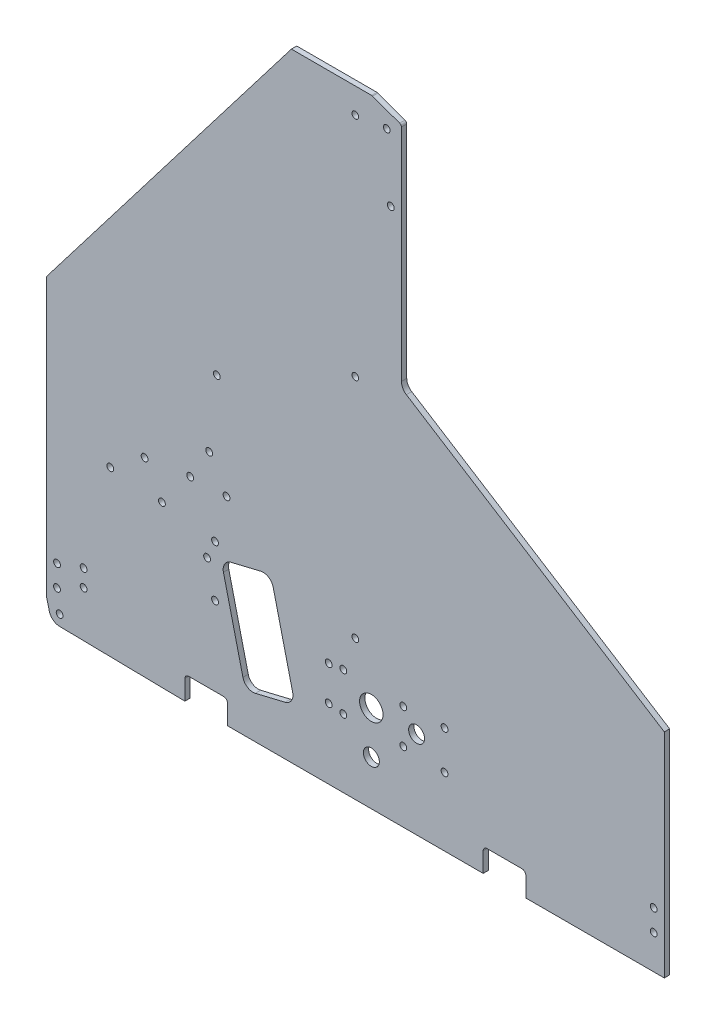
SolidWorks part; units mm, degrees
ref_plane "Front Plane" through (0, 0, 0) normal (0, 0, 1) x (1, 0, 0)
ref_plane "Top Plane" through (0, 0, 0) normal (0, 1, 0) x (1, 0, 0)
ref_plane "Right Plane" through (0, 0, 0) normal (1, 0, 0) x (0, 0, -1)
sketch "Sketch1" plane through (0, 0, 0) normal (0, 0, 1) x (1, 0, 0)
  line L0 (82.55, -20.32) -> (82.55, -6.35)
  line L2 (0, 0) -> (0, 157.48)
  line L4 (368.3, -20.32) -> (368.3, 106.68)
  line L5 (82.55, -6.35) -> (107.95, -6.35)
  line L6 (107.95, -6.35) -> (107.95, -20.32)
  line L7 (107.95, -20.32) -> (260.35, -20.32)
  line L8 (260.35, -20.32) -> (260.35, -6.35)
  line L9 (260.35, -6.35) -> (285.75, -6.35)
  line L10 (285.75, -6.35) -> (285.75, -20.32)
  line L11 (285.75, -20.32) -> (368.3, -20.32)
  line L12 (361.95, 12.7) -> (368.3, 12.7) construction
  line L13 (0, 0) -> (6.35, 0) construction
  line L14 (0.1896, -7.8901) -> (1.7771, -14.2401)
  line L15 (7.8295, -19.0491) -> (82.55, -20.32)
  line L16 (0, 0) -> (0, -6.35)
  line L17 (85.725, 97.155) -> (82.9754, 95.5675) construction
  line L18 (97.0634, 115.6163) -> (58.5686, 93.3913) construction
  line L19 (97.0634, 115.6163) -> (107.3822, 97.7437) construction
  line L20 (58.5686, 93.3913) -> (68.8873, 75.5187) construction
  line L21 (107.3822, 97.7437) -> (68.8873, 75.5187) construction
  line L22 (97.0634, 115.6163) -> (68.8873, 75.5187) construction
  line L23 (58.5686, 93.3913) -> (107.3822, 97.7437) construction
  line L24 (7.9375, -12.7) -> (95.7973, 60.4105) construction
  line L25 (184.15, 62.98) -> (184.15, 197.98) construction
  line L26 (184.15, 197.98) -> (184.15, 332.98) construction
  line L27 (355.6, 335.28) -> (330.2, 335.28) construction
  line L28 (330.2, 335.28) -> (330.2, 220.98) construction
  line L29 (330.2, 220.98) -> (355.6, 220.98) construction
  line L30 (355.6, 220.98) -> (355.6, 335.28) construction
  line L31 (184.15, 347.98) -> (184.15, 269.4703) construction
  line L32 (12.7, 335.28) -> (38.1, 335.28) construction
  line L33 (38.1, 335.28) -> (38.1, 220.98) construction
  line L34 (12.7, 220.98) -> (12.7, 335.28) construction
  line L35 (38.1, 220.98) -> (12.7, 220.98) construction
  line L36 (194.15, 347.98) -> (211.6138, 341.63)
  line L37 (184.15, 347.98) -> (146.05, 347.98)
  line L38 (184.15, 347.98) -> (194.15, 347.98)
  line L39 (348.5362, 347.98) -> (413.4623, 347.98)
  line L40 (348.5362, 347.98) -> (211.6138, 347.98) construction
  line L42 (146.05, 347.98) -> (0, 157.48)
  line L44 (211.6138, 341.63) -> (211.6138, 205.74)
  line L45 (211.6138, 205.74) -> (368.3, 106.68)
  line L46 (194.15, 347.98) -> (-141.0713, 347.98) construction
  circle A0 centre (6.35, 0) radius 2.032
  circle A1 centre (6.35, 12.7) radius 2.032
  circle A2 centre (361.95, 0) radius 2.032
  circle A3 centre (361.95, 12.7) radius 2.032
  arc A5 (1.7771, -14.2401) -> (7.8295, -19.0491) centre (7.9375, -12.7) ccw
  circle A6 centre (7.9375, -12.7) radius 2.032
  arc A7 (0, -6.35) -> (0.1896, -7.8901) centre (6.35, -6.35) ccw
  circle A8 centre (38.1, 78.105) radius 2.032
  circle A9 centre (85.725, 97.155) radius 2.032
  circle A10 centre (58.5686, 93.3913) radius 2.032
  circle A11 centre (68.8873, 75.5187) radius 2.032
  circle A12 centre (107.3822, 97.7437) radius 2.032
  circle A13 centre (97.0634, 115.6163) radius 2.032
  circle A14 centre (95.7973, 60.4105) radius 2.032
  circle A15 centre (184.15, 62.98) radius 2
  circle A16 centre (184.15, 197.98) radius 2
  circle A17 centre (184.15, 332.98) radius 2
  circle A18 centre (63.5, 316.23) radius 2.032
  circle A19 centre (101.6, 157.48) radius 2.032
  circle A20 centre (355.6, 335.28) radius 2.032
  circle A21 centre (330.2, 335.28) radius 2.032
  circle A22 centre (355.6, 220.98) radius 2.032
  circle A23 centre (330.2, 220.98) radius 2.032
  circle A24 centre (12.7, 335.28) radius 2.032
  circle A25 centre (38.1, 335.28) radius 2.032
  circle A26 centre (12.7, 220.98) radius 2.032
  circle A27 centre (38.1, 220.98) radius 2.032
  circle A28 centre (202.8819, 335.28) radius 2
  circle A29 centre (205.2638, 296.418) radius 2.032
  point P82 (184.15, 347.98)
  point P83 (202.8819, 344.805)
  dimension "D6" = 4.064
  dimension "D10" = 6.35
  dimension "D11" = 4.064
  dimension "D17" = 38.1
  dimension "D27" = 4
  dimension "D31" = 4.064
  dimension "D32" = 38.1
  dimension "D36" = 4.064
  dimension "D47" = 45.212
  dimension "D48" = 4.064
  dimension "D2" = 127
  dimension "D3" = 13.97
  dimension "D4" = 25.4
  dimension "D5" = 152.4
  dimension "D7" = 12.7
  dimension "D8" = 6.35
  dimension "D9" = 20.32
  dimension "D12" = 12.7
  dimension "D13" = 1.5875
  dimension "D14" = 82.55
  dimension "D15" = 368.3
  dimension "D16" = 6.35
  dimension "D18" = 98.425
  dimension "D19" = 47.625
  dimension "D20" = 19.05
  dimension "D21" = 3.175
  dimension "D22" = 60
  dimension "D23" = 20.6375
  dimension "D24" = 44.45
  dimension "D25" = 38.1
  dimension "D26" = 114.3
  dimension "D28" = 135
  dimension "D29" = 12.7
  dimension "D30" = 15
  dimension "D33" = 63.5
  dimension "D34" = 27.4638
  dimension "D35" = 101.6
  dimension "D37" = 114.3
  dimension "D38" = 25.4
  dimension "D39" = 12.7
  dimension "D40" = 157.48
  dimension "D41" = 142.24
  dimension "D42" = 368.3
  dimension "D43" = 10
  dimension "D44" = 6.35
  dimension "D45" = 31.75
  dimension "D46" = 6.35
  dimension "D49" = 6.35
extrude "Boss-Extrude1" add sketch "Sketch1" along normal blind 3.175 contours L16 A7 L14 A5 L15 L2 A0 A1 A6 region at (167.8922, 118.3155, 0)
fillet "Fillet1" radius 2.286 4 edges at (285.75, -6.35, 1.5875) (107.95, -6.35, 1.5875) (260.35, -6.35, 1.5875) (82.55, -6.35, 1.5875)
fillet "Fillet2" radius 6.35 1 edges at (211.6138, 205.74, 1.5875)
sketch "Sketch2" plane through (0, 0, 0) normal (0, 0, -1) x (-1, 0, 0)
  circle A0 centre (-100.5528, 71.086) radius 2.032 construction
  circle A1 centre (-100.5528, 40.606) radius 2.032 construction
  circle A2 centre (-22.225, 18.2025) radius 2.032 construction
  circle A3 centre (-22.225, 8.0425) radius 2.032 construction
  circle A4 centre (-100.5528, 71.086) radius 2.032
  circle A5 centre (-100.5528, 40.606) radius 2.032
  circle A6 centre (-22.225, 18.2025) radius 2.032
  circle A7 centre (-22.225, 8.0425) radius 2.032
extrude "Cut-Extrude1" cut sketch "Sketch2" against normal through all
fillet "Fillet3" radius 1.5875 2 edges at (211.6138, 341.63, 1.5875) (194.15, 347.98, 1.5875)
sketch "Sketch3" plane through (0, 0, 3.175) normal (0, 0, 1) x (1, 0, 0)
  line L0 (132.9524, 63.2646) -> (132.7215, 64.2281) construction
  line L1 (128.3814, 66.8897) -> (110.6828, 62.6472) construction
  line L2 (114.5132, 58.4237) -> (126.8822, 61.3887) construction
  line L3 (108.0212, 58.3071) -> (108.2522, 57.3436) construction
  line L4 (131.2006, 57.703) -> (140.0164, 20.9265) construction
  line L5 (144.0993, 16.7636) -> (132.9524, 63.2646) construction
  line L6 (108.2522, 57.3436) -> (119.3991, 10.8426) construction
  line L7 (121.1509, 16.4042) -> (112.3351, 53.1807) construction
  line L8 (119.3991, 10.8426) -> (119.6301, 9.8791) construction
  line L9 (144.3303, 15.8001) -> (144.0993, 16.7636) construction
  line L10 (137.8383, 15.6835) -> (125.4694, 12.7185) construction
  line L11 (123.9701, 7.2175) -> (141.6687, 11.4601) construction
  line L12 (132.9524, 63.2646) -> (132.7215, 64.2281)
  line L13 (128.3814, 66.8897) -> (110.6828, 62.6472)
  line L14 (114.5132, 58.4237) -> (126.8822, 61.3887)
  line L15 (108.0212, 58.3071) -> (108.2522, 57.3436)
  line L16 (131.2006, 57.703) -> (140.0164, 20.9265)
  line L17 (144.0993, 16.7636) -> (132.9524, 63.2646)
  line L18 (108.2522, 57.3436) -> (119.3991, 10.8426)
  line L19 (121.1509, 16.4042) -> (112.3351, 53.1807)
  line L20 (119.3991, 10.8426) -> (119.6301, 9.8791)
  line L21 (144.3303, 15.8001) -> (144.0993, 16.7636)
  line L22 (137.8383, 15.6835) -> (125.4694, 12.7185)
  line L23 (123.9701, 7.2175) -> (141.6687, 11.4601)
  line L24 (127.7894, 69.3598) -> (110.0908, 65.1172)
  line L25 (105.5512, 57.715) -> (105.7822, 56.7515)
  line L26 (105.7822, 56.7515) -> (116.9291, 10.2505)
  line L27 (116.9291, 10.2505) -> (117.16, 9.287)
  line L28 (124.5622, 4.7475) -> (142.2608, 8.99)
  line L29 (146.8003, 16.3922) -> (146.5694, 17.3557)
  line L30 (146.5694, 17.3557) -> (135.4225, 63.8567)
  line L31 (135.4225, 63.8567) -> (135.1915, 64.8202)
  arc A0 (132.7215, 64.2281) -> (128.6308, 66.9403) centre (129.2206, 63.3889) ccw construction
  arc A1 (110.6828, 62.6472) -> (110.4377, 62.5791) centre (111.522, 59.1463) ccw construction
  arc A2 (128.6308, 66.9403) -> (128.3814, 66.8897) centre (129.2206, 63.3889) ccw construction
  arc A3 (110.4377, 62.5791) -> (108.0212, 58.3071) centre (111.522, 59.1463) ccw construction
  arc A4 (119.6301, 9.8791) -> (123.7207, 7.1669) centre (123.1309, 10.7183) ccw construction
  arc A5 (141.9139, 11.5281) -> (144.3303, 15.8001) centre (140.8295, 14.9609) ccw construction
  arc A6 (141.6687, 11.4601) -> (141.9139, 11.5281) centre (140.8295, 14.9609) ccw construction
  arc A7 (123.7207, 7.1669) -> (123.9701, 7.2175) centre (123.1309, 10.7183) ccw construction
  arc A8 (132.7215, 64.2281) -> (128.6308, 66.9403) centre (129.2206, 63.3889) ccw
  arc A9 (110.6828, 62.6472) -> (110.4377, 62.5791) centre (111.522, 59.1463) ccw
  arc A10 (128.6308, 66.9403) -> (128.3814, 66.8897) centre (129.2206, 63.3889) ccw
  arc A11 (110.4377, 62.5791) -> (108.0212, 58.3071) centre (111.522, 59.1463) ccw
  arc A12 (119.6301, 9.8791) -> (123.7207, 7.1669) centre (123.1309, 10.7183) ccw
  arc A13 (141.9139, 11.5281) -> (144.3303, 15.8001) centre (140.8295, 14.9609) ccw
  arc A14 (141.6687, 11.4601) -> (141.9139, 11.5281) centre (140.8295, 14.9609) ccw
  arc A15 (123.7207, 7.1669) -> (123.9701, 7.2175) centre (123.1309, 10.7183) ccw
  arc A16 (110.0908, 65.1172) -> (109.6726, 65.0012) centre (111.522, 59.1463) ccw
  arc A17 (109.6726, 65.0012) -> (105.5512, 57.715) centre (111.522, 59.1463) ccw
  arc A18 (117.16, 9.287) -> (124.1369, 4.6613) centre (123.1309, 10.7183) ccw
  arc A19 (124.1369, 4.6613) -> (124.5622, 4.7475) centre (123.1309, 10.7183) ccw
  arc A20 (142.2608, 8.99) -> (142.6789, 9.1061) centre (140.8295, 14.9609) ccw
  arc A21 (142.6789, 9.1061) -> (146.8003, 16.3922) centre (140.8295, 14.9609) ccw
  arc A22 (135.1915, 64.8202) -> (128.2147, 69.446) centre (129.2206, 63.3889) ccw
  arc A23 (128.2147, 69.446) -> (127.7894, 69.3598) centre (129.2206, 63.3889) ccw
  ellipse E0 centre (124.5974, 48.8487) end of major axis (128.5376, 61.3578) minor radius 6 (131.2006, 57.703) -> (126.8822, 61.3887) ccw construction
  ellipse E1 centre (122.2349, 48.2824) end of major axis (113.0518, 57.6456) minor radius 6 (114.5132, 58.4237) -> (112.3351, 53.1807) ccw construction
  ellipse E2 centre (127.7541, 25.2585) end of major axis (131.6942, 37.7675) minor radius 6 (121.1509, 16.4042) -> (125.4694, 12.7185) ccw construction
  ellipse E3 centre (130.1166, 25.8248) end of major axis (139.2998, 16.4616) minor radius 6 (137.8383, 15.6835) -> (140.0164, 20.9265) ccw construction
  ellipse E4 centre (124.5974, 48.8487) end of major axis (128.5376, 61.3578) minor radius 6 (131.2006, 57.703) -> (126.8822, 61.3887) ccw
  ellipse E5 centre (122.2349, 48.2824) end of major axis (131.4181, 38.9192) minor radius 6 (114.5132, 58.4237) -> (112.3351, 53.1807) ccw
  ellipse E6 centre (127.7541, 25.2585) end of major axis (123.8139, 12.7495) minor radius 6 (121.1509, 16.4042) -> (125.4694, 12.7185) ccw
  ellipse E7 centre (130.1166, 25.8248) end of major axis (139.2998, 16.4616) minor radius 6 (137.8383, 15.6835) -> (140.0164, 20.9265) ccw
  dimension "D1" = 2.54
extrude "Cut-Extrude2" cut sketch "Sketch3" against normal through all contours A22 A23 L24 A16 A17 L25 L26 L27 A18 A19 L28 A20 A21 L29 L30 L31 A15 A12 L20 L18 L15 A11 A9 L13 A10 A8 L12 L17 L21 A13 A14 L23 | A12 A15 L23 A14 A13 L21 L17 L12 A8 A10 L13 A9 A11 L15 L18 L20 E7 L22 E6 L19 E5 L14 E4 L16 | L22 E7 L16 E4 L14 E5 L19 E6 region at (137.844, 39.8506, 3.175) region at (126.1758, 37.0536, 3.175) region at (128.1544, 68.6507, 3.175)
sketch "Sketch4" plane through (0, 0, 3.175) normal (0, 0, 1) x (1, 0, 0)
  line L0 (107.3822, 97.7437) -> (68.8873, 75.5187) construction
  line L1 (168.275, 21.4312) -> (212.725, 21.4312) construction
  line L2 (168.275, 21.4312) -> (168.275, 42.0687) construction
  line L3 (168.275, 42.0687) -> (212.725, 42.0687) construction
  line L4 (212.725, 21.4312) -> (212.725, 42.0687) construction
  line L5 (168.275, 21.4312) -> (212.725, 42.0687) construction
  line L6 (168.275, 42.0687) -> (212.725, 21.4312) construction
  line L7 (97.0634, 115.6163) -> (107.3822, 97.7437) construction
  line L8 (107.95, -20.32) -> (260.35, -20.32) construction
  line L9 (193.675, 31.75) -> (177.005, 31.75) construction
  line L10 (190.5, 31.75) -> (193.675, 31.75) construction
  line L11 (6.35, 12.7) -> (361.95, 12.7) construction
  line L12 (107.95, -6.35) -> (107.95, -20.32) construction
  line L13 (193.675, 31.75) -> (220.6625, 31.75) construction
  line L14 (177.005, 20.2819) -> (177.005, 43.2181) construction
  line L15 (194.15, 47.98) -> (174.15, 47.98) construction
  line L16 (194.15, 47.98) -> (194.15, 347.98) construction
  line L17 (194.15, 347.98) -> (174.15, 347.98) construction
  line L18 (174.15, 47.98) -> (174.15, 347.98) construction
  line L19 (194.15, 47.98) -> (174.15, 347.98) construction
  line L20 (194.15, 347.98) -> (174.15, 47.98) construction
  circle A0 centre (168.275, 42.0687) radius 2.032
  circle A1 centre (212.725, 42.0687) radius 2.032
  circle A2 centre (212.725, 21.4312) radius 2.032
  circle A3 centre (168.275, 21.4312) radius 2.032
  circle A4 centre (193.675, 31.75) radius 6.985
  circle A5 centre (220.6625, 31.75) radius 4.7625
  circle A7 centre (220.6625, 31.75) radius 14.2875 construction
  circle A8 centre (193.675, 31.75) radius 12.7 construction
  circle A9 centre (177.005, 43.2181) radius 2.032
  circle A10 centre (177.005, 20.2819) radius 2.032
  circle A11 centre (237.33, 43.2181) radius 2.032
  circle A12 centre (237.33, 20.2819) radius 2.032
  circle A13 centre (193.675, 6.35) radius 4.7625
  point P0 (190.5, 31.75)
  point P26 (184.15, 197.98)
  point P38 (177.005, 31.75)
  dimension "D1" = 4.064
  dimension "D4" = 13.97
  dimension "D7" = 9.525
  dimension "D10" = 25.4
  dimension "D11" = 28.575
  dimension "D2" = 52.07
  dimension "D3" = 3.175
  dimension "D5" = 82.55
  dimension "D6" = 26.9875
  dimension "D8" = 20
  dimension "D9" = 300
  dimension "D12" = 16.67
  dimension "D13" = 22.9362
  dimension "D14" = 60.325
  dimension "D15" = 25.4
extrude "Cut-Extrude3" cut sketch "Sketch4" against normal through all
